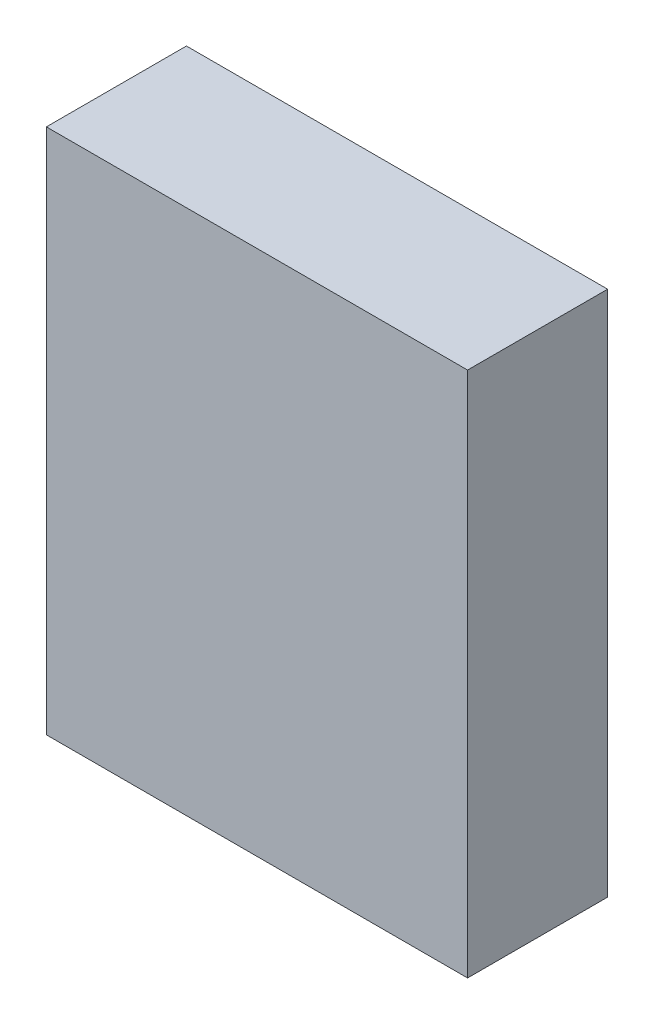
SolidWorks part; units mm, degrees
material "AISI 1045 Steel, cold drawn"
ref_plane "Front Plane" through (0, 0, 0) normal (0, 0, 1) x (1, 0, 0)
ref_plane "Top Plane" through (0, 0, 0) normal (0, 1, 0) x (1, 0, 0)
ref_plane "Right Plane" through (0, 0, 0) normal (1, 0, 0) x (0, 0, -1)
sketch "Sketch1" plane through (0, 0, 0) normal (0, 0, 1) x (1, 0, 0)
  line L1 (200, -250) -> (-200, -250)
  line L2 (200, -250) -> (200, 250)
  line L3 (200, 250) -> (-200, 250)
  line L4 (-200, -250) -> (-200, 250)
  line L5 (200, -250) -> (-200, 250) construction
  line L6 (200, 250) -> (-200, -250) construction
  point P0 (0, 0)
  dimension "D1" = 500
  dimension "D2" = 400
extrude "Boss-Extrude1" add sketch "Sketch1" along normal blind 150
sketch "Sketch2" plane through (0, 0, 0) normal (0, 0, -1) x (-1, 0, 0)
  line L1 (177.5, -230) -> (-177.5, -230)
  line L2 (177.5, -230) -> (177.5, 230)
  line L3 (177.5, 230) -> (-177.5, 230)
  line L4 (200, -250) -> (200, 250)
  line L5 (200, 250) -> (-200, 250)
  line L6 (-200, 250) -> (-200, -250)
  line L7 (-200, -250) -> (200, -250)
  line L8 (200, -250) -> (200, 250)
  line L9 (200, 250) -> (-200, 250)
  line L10 (-200, 250) -> (-200, -250)
  line L11 (-200, -250) -> (200, -250)
  line L12 (-177.5, -230) -> (-177.5, 230)
  line L13 (177.5, -230) -> (-177.5, 230) construction
  line L14 (177.5, 230) -> (-177.5, -230) construction
  point P2 (0, 0)
  dimension "D2" = 355
  dimension "D3" = 460
  dimension "D1" = 0
extrude "Cut-Extrude1" cut sketch "Sketch2" against normal blind 17
shell "Shell1" thickness 1.5 removed face at (0, 0, 0)
sketch "Sketch3" plane through (0, 0, 148.5) normal (0, 0, -1) x (-1, 0, 0)
  line L1 (162.5, -202.5) -> (-162.5, -202.5) construction
  line L2 (162.5, -202.5) -> (162.5, 202.5) construction
  line L3 (162.5, 202.5) -> (-162.5, 202.5) construction
  line L4 (-162.5, -202.5) -> (-162.5, 202.5) construction
  line L5 (162.5, -202.5) -> (-162.5, 202.5) construction
  line L6 (162.5, 202.5) -> (-162.5, -202.5) construction
  circle A0 centre (-162.5, 202.5) radius 7.5
  circle A1 centre (162.5, 202.5) radius 7.5
  circle A2 centre (162.5, -202.5) radius 7.5
  circle A3 centre (-162.5, -202.5) radius 7.5
  point P0 (0, 0)
  dimension "D3" = 15
  dimension "D1" = 325
  dimension "D2" = 405
extrude "Boss-Extrude2" add sketch "Sketch3" along normal blind 14
sketch "Sketch4" plane through (198.5, 0, 0) normal (-1, 0, 0) x (0, 0, 1)
  line L0 (148.5, -248.5) -> (18.5, -248.5) construction
  line L1 (18.5, 228.5) -> (18.5, -228.5) construction
  circle A0 centre (43.5, -188.5) radius 3
  dimension "D3" = 6
  dimension "D1" = 60
  dimension "D2" = 25
extrude "Boss-Extrude3" add sketch "Sketch4" along normal blind 12.5
